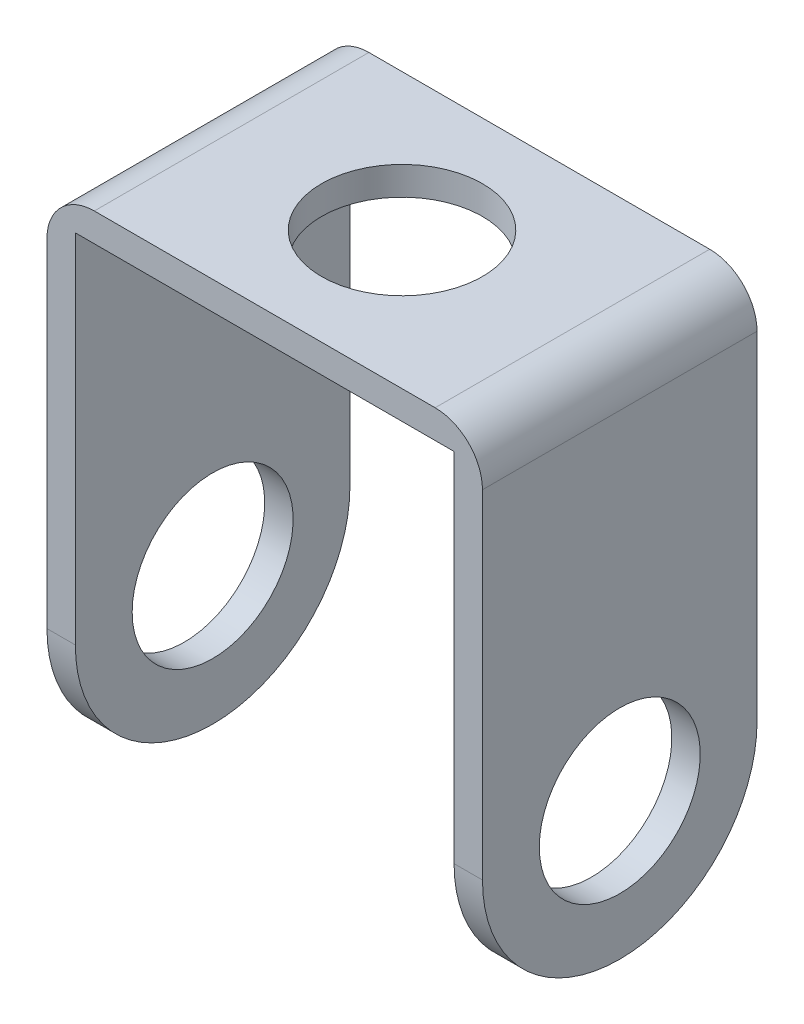
SolidWorks part; units mm, degrees
ref_plane "Front Plane" through (0, 0, 0) normal (0, 0, 1) x (1, 0, 0)
ref_plane "Top Plane" through (0, 0, 0) normal (0, 1, 0) x (1, 0, 0)
ref_plane "Right Plane" through (0, 0, 0) normal (1, 0, 0) x (0, 0, -1)
sketch "Sketch1" plane through (0, 0, 0) normal (0, 0, 1) x (1, 0, 0)
  line L0 (0, -55) -> (0, 55) construction
  line L1 (10.75, 13.05) -> (10.75, 13.8) construction
  line L2 (0, 0) -> (0, 12.55)
  line L3 (1.25, 13.8) -> (10.25, 13.8)
  line L4 (11.5, 12.55) -> (11.5, 0)
  line L5 (55, 0) -> (-55, 0) construction
  line L6 (11.5, 0) -> (10.75, 0)
  line L7 (10.75, 0) -> (10.75, 13.05)
  line L8 (0.75, 13.05) -> (0.75, 0)
  line L9 (0.75, 0) -> (0, 0)
  line L10 (0.75, 13.05) -> (10.75, 13.05)
  line L11 (0.75, 13.05) -> (0, 13.05) construction
  arc A0 (0, 12.55) -> (1.25, 13.8) centre (1.25, 12.55) cw
  arc A1 (10.25, 13.8) -> (11.5, 12.55) centre (10.25, 12.55) cw
  point P17 (0, 13.8)
  point P20 (11.5, 13.8)
  dimension "D4" = 1.25
  dimension "D1" = 11.5
  dimension "D2" = 13.8
  dimension "D3" = 0.75
extrude "Boss-Extrude1" add sketch "Sketch1" along normal blind 7.25
sketch "Sketch2" plane through (0, 0, 0) normal (-1, 0, 0) x (0, 0, 1)
  line L0 (3.625, 0) -> (3.625, 3.625) construction
  line L1 (7.25, 0) -> (0, 0) construction
  line L2 (3.625, 0) -> (7.25, 0)
  line L3 (7.25, 0) -> (7.25, 3.625)
  line L4 (3.625, 0) -> (0, 0)
  line L5 (0, 0) -> (0, 3.625)
  circle A0 centre (3.625, 3.625) radius 3.625
  circle A1 centre (3.625, 3.625) radius 2.125
  line M1 (0, 12.55) -> (0, 0)
  line M2 (0, 0) -> (7.25, 0)
  line M3 (7.25, 0) -> (7.25, 12.55)
  dimension "D2" = 4.25
  dimension "D1" = 3.625
extrude "Cut-Extrude1" cut sketch "Sketch2" against normal mid plane 100 contours A0 M1 M2 region at (0, 0.8097, 0.8097)
extrude "Cut-Extrude2" cut sketch "Sketch2<3>" against normal mid plane 100 contours A0 M2 M3 region at (0, 0.8097, 6.4403)
sketch "Sketch2<3>" plane through (0, 0, 0) normal (-1, 0, 0) x (0, 0, 1) same geometry as "Sketch2"
extrude "Cut-Extrude3" cut sketch "Sketch2<4>" against normal mid plane 100 contours A1 region at (0, 3.625, 3.625)
sketch "Sketch2<4>" plane through (0, 0, 0) normal (-1, 0, 0) x (0, 0, 1) same geometry as "Sketch2"
sketch "Sketch6" plane through (0, 13.8, 0) normal (0, 1, 0) x (1, 0, 0)
  line L0 (1.25, -3.625) -> (10.25, -3.625) construction
  line L1 (1.25, -7.25) -> (1.25, 0) construction
  line L2 (10.25, -7.25) -> (10.25, 0) construction
  line L3 (5.75, -7.25) -> (5.75, -3.625) construction
  line L4 (10.25, -7.25) -> (1.25, -7.25) construction
  circle A0 centre (5.75, -3.625) radius 2.125
  dimension "D1" = 4.25
extrude "Cut-Extrude4" cut sketch "Sketch6" against normal mid plane 100
